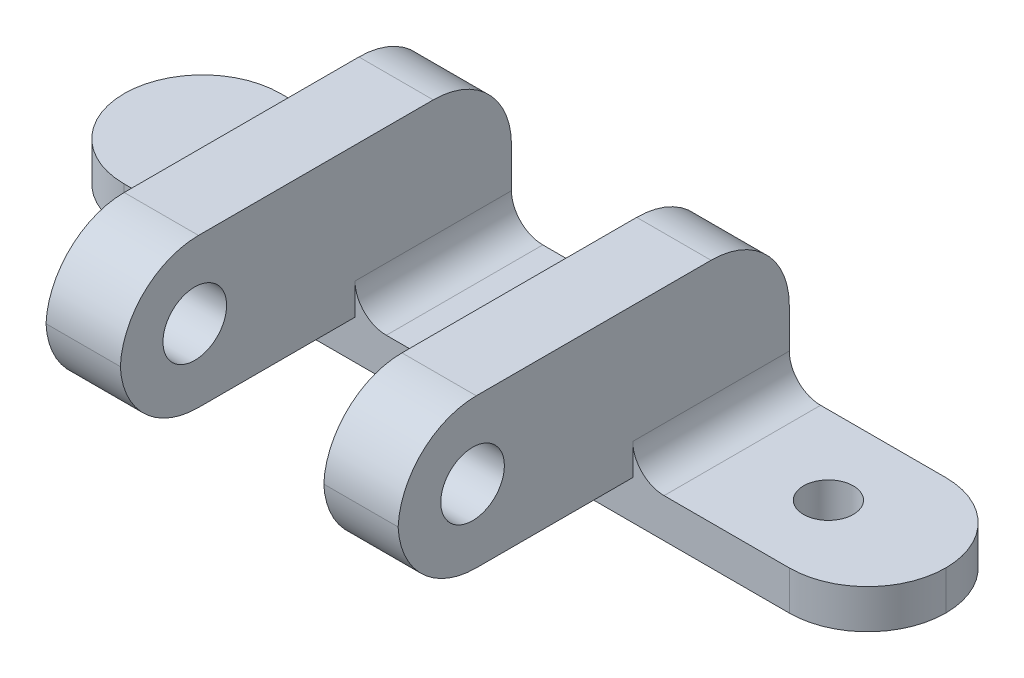
SolidWorks part; units mm, degrees
ref_plane "Front" through (0, 0, 0) normal (0, 0, 1) x (1, 0, 0)
ref_plane "Top" through (0, 0, 0) normal (0, 1, 0) x (1, 0, 0)
ref_plane "Right" through (0, 0, 0) normal (1, 0, 0) x (0, 0, -1)
sketch "Sketch1" plane through (0, 0, 0) normal (0, 1, 0) x (1, 0, 0)
  line L1 (-22.5, -10) -> (22.5, -10)
  line L2 (-22.5, -10) -> (-22.5, 10)
  line L3 (-22.5, 10) -> (22.5, 10)
  line L4 (22.5, -10) -> (22.5, 10)
  line L5 (-22.5, -10) -> (22.5, 10) construction
  line L6 (-22.5, 10) -> (22.5, -10) construction
  point P0 (0, 0)
  dimension "D1" = 45
  dimension "D2" = 20
extrude "Boss-Extrude1" add sketch "Sketch1" along normal blind 5
sketch "Sketch2" plane through (0, 5, 0) normal (0, 1, 0) x (1, 0, 0)
  line L0 (-22.5, -10) -> (22.5, -10) construction
  line L1 (22.5, 10) -> (13, 10)
  line L2 (22.5, 10) -> (22.5, -10)
  line L3 (22.5, -10) -> (13, -10)
  line L4 (13, 10) -> (13, -10)
  line L6 (-22.5, 10) -> (-13, 10)
  line L7 (-22.5, 10) -> (-22.5, -10)
  line L8 (-22.5, -10) -> (-13, -10)
  line L9 (-13, 10) -> (-13, -10)
  dimension "D1" = 9.5
extrude "Boss-Extrude2" add sketch "Sketch2" along normal blind 19.05
sketch "Sketch3" plane through (0, 0, 10) normal (0, 0, 1) x (1, 0, 0)
  line L0 (-13, 24.05) -> (-13, 5) construction
  line L1 (-22.5, 24.05) -> (-13, 24.05)
  line L2 (-22.5, 24.05) -> (-22.5, 5)
  line L3 (-22.5, 5) -> (-13, 5)
  line L4 (-13, 24.05) -> (-13, 5)
  line L5 (22.5, 24.05) -> (22.5, 0) construction
  line L6 (13, 24.05) -> (22.5, 24.05)
  line L7 (13, 24.05) -> (13, 5)
  line L8 (13, 5) -> (22.5, 5)
  line L9 (22.5, 24.05) -> (22.5, 5)
  dimension "D1" = 19.05
extrude "Boss-Extrude3" add sketch "Sketch3" along normal blind 30
sketch "Sketch4" plane through (22.5, 0, 0) normal (1, 0, 0) x (0, 0, -1)
  line L0 (-40, 14.525) -> (10, 14.525) construction
  line L1 (-40, 5) -> (-40, 24.05) construction
  line L2 (10, 24.05) -> (10, 0) construction
  circle A0 centre (-30.475, 14.525) radius 4.064
  dimension "D1" = 8.128
  dimension "D2" = 9.525
extrude "Cut-Extrude1" cut sketch "Sketch4" against normal through all
sketch "Sketch8" plane through (0, 5, 0) normal (0, 1, 0) x (1, 0, 0)
  line L0 (-6.0424, 10) -> (49987.3033, 10) construction
  line L3 (-13, -10) -> (13, -10) construction
  line L4 (-22.5, -26.411) -> (-22.5, -34.539) construction
  line L5 (22.5, -10) -> (52.5, -10)
  line L6 (22.5, -10) -> (22.5, 10)
  line L7 (22.5, 10) -> (52.5, 10)
  line L8 (52.5, -10) -> (52.5, 10)
  line L9 (-22.5, -10) -> (-52.5, -10)
  line L10 (-22.5, -10) -> (-22.5, 10)
  line L11 (-22.5, 10) -> (-52.5, 10)
  line L12 (-52.5, -10) -> (-52.5, 10)
  line L13 (13, 10) -> (-13, 10) construction
  point P6 (0, -10)
  point P17 (-22.5, 11.2237)
  point P22 (-22.5, -10)
  dimension "D1" = 30
extrude "Boss-Extrude4" add sketch "Sketch8" against normal up to surface (5 mm away) up to face at (0, 0, 0)
sketch "Sketch5" plane through (0, 5, 0) normal (0, 1, 0) x (1, 0, 0)
  line L0 (37.5, 10) -> (37.5, -10) construction
  line L1 (13, 10) -> (-13, 10) construction
  line L2 (-13, -10) -> (13, -10) construction
  line L3 (-37.5, 10) -> (-37.5, -10) construction
  line L4 (37.5, 0) -> (-37.5, 0) construction
  line L5 (52.5, 10) -> (22.5, 10) construction
  line L6 (-22.5, 10) -> (-52.5, 10) construction
  point P11 (37.5, 10)
  point P14 (-37.5, 10)
hole_wizard "1/4 (0.25) Diameter Hole1" positions "Sketch6" profile "Sketch7" hole size "1/4" standard "ANSI Inch" end condition up to next
sketch "Sketch6" plane through (0, 5, 0) normal (0, 1, 0) x (1, 0, 0)
  point P0 (37.5, 0)
  point P3 (-37.5, 0)
sketch "Sketch7" plane through (37.5, 5, 0) normal (1, 0, 0) x (0, 0, 1)
  line L0 (0, 0) -> (0, 5)
  line L1 (0, 5) -> (3.175, 5)
  line L2 (3.175, 5) -> (3.175, 0)
  line L5 (3.175, 0) -> (0, 0)
  line L11 (0, -6.35) -> (0, 107.95) construction
  dimension "Thru Hole Dia." = 6.35
  dimension "Thru Hole Depth" = 5
fillet "Fillet1" radius 10 10 edges at (-17.75, 24.05, -10) (-17.75, 5, 40) (-17.75, 24.05, 40) (17.75, 5, 40) (17.75, 24.05, 40) (17.75, 24.05, -10) (52.5, 2.5, 10) (52.5, 2.5, -10) (-52.5, 2.5, 10) (-52.5, 2.5, -10)
fillet "Fillet2" radius 4 4 edges at (22.5, 5, 0) (-22.5, 5, 0) (-13, 5, 0) (13, 5, 0)
